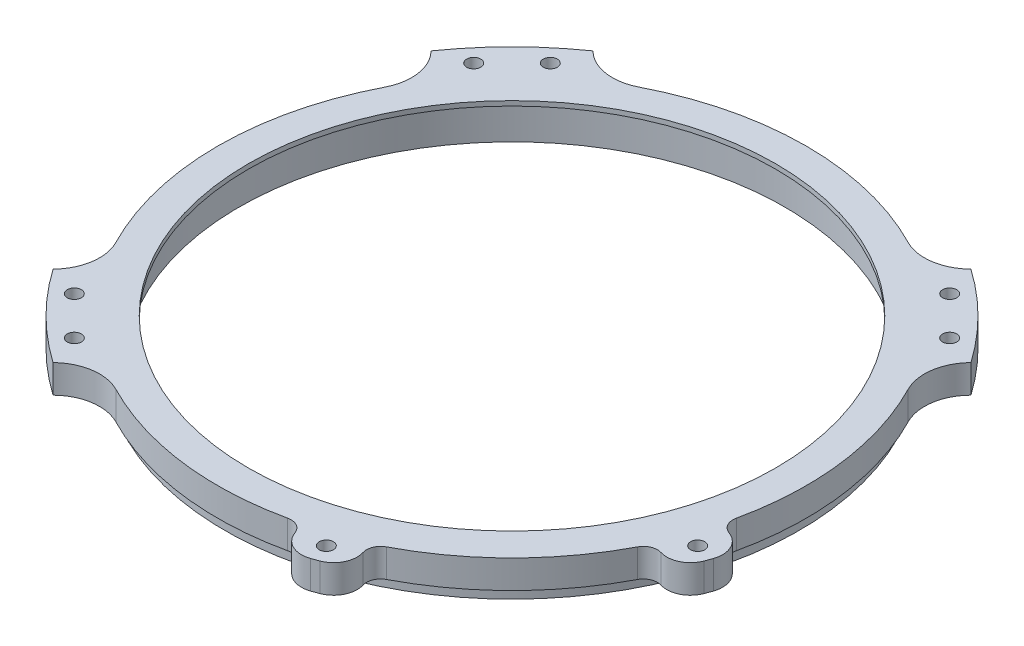
SolidWorks part; units mm, degrees
material "6061 合金"
ref_plane "前视基准面" through (0, 0, 0) normal (0, 0, 1) x (1, 0, 0)
ref_plane "上视基准面" through (0, 0, 0) normal (0, 1, 0) x (1, 0, 0)
ref_plane "右视基准面" through (0, 0, 0) normal (1, 0, 0) x (0, 0, -1)
sketch "草图1" plane through (0, 0, 0) normal (0, 1, 0) x (1, 0, 0)
  circle A0 centre (0, 0) radius 70
  circle A1 centre (0, 0) radius 58
  dimension "D1" = 140
  dimension "D2" = 116
extrude "凸台-拉伸1" add sketch "草图1" along normal blind 9
sketch "草图3" plane through (0, 0, 0) normal (0, -1, 0) x (1, 0, 0)
  circle A0 centre (0, 0) radius 70
  circle A1 centre (0, 0) radius 61
  dimension "D1" = 122
  dimension "D2" = 140
extrude "切除-拉伸2" cut sketch "草图3" against normal blind 3
sketch "草图4" plane through (0, 9, 0) normal (0, 1, 0) x (1, 0, 0)
  line L0 (0, 0) -> (0, 70) construction
  line L1 (35.8485, 51.197) -> (40.1504, 57.3406)
  line L2 (51.197, 35.8485) -> (57.3406, 40.1504)
  line L3 (60.3704, -16.1762) -> (67.6148, -18.1173)
  line L4 (16.1762, -60.3704) -> (18.1173, -67.6148)
  line L5 (-35.8485, -51.197) -> (-40.1504, -57.3406)
  line L6 (-51.197, -35.8485) -> (-57.3406, -40.1504)
  line L7 (-51.197, 35.8485) -> (-57.3406, 40.1504)
  line L8 (-35.8485, 51.197) -> (-40.1504, 57.3406)
  line L9 (0, 0) -> (35.8485, 51.197) construction
  line L10 (0, 0) -> (51.197, 35.8485) construction
  line L11 (16.1762, -60.3704) -> (0, 0) construction
  line L12 (60.3704, -16.1762) -> (0, 0) construction
  line L13 (0, 0) -> (0, -70) construction
  arc A0 (-51.197, 35.8485) -> (-51.197, -35.8485) centre (0, 0) ccw
  arc A1 (-57.3406, 40.1504) -> (-57.3406, -40.1504) centre (0, 0) ccw
  arc A2 (-35.8485, -51.197) -> (16.1762, -60.3704) centre (0, 0) ccw
  arc A3 (-40.1504, -57.3406) -> (18.1173, -67.6148) centre (0, 0) ccw
  arc A4 (60.3704, -16.1762) -> (51.197, 35.8485) centre (0, 0) ccw
  arc A5 (67.6148, -18.1173) -> (57.3406, 40.1504) centre (0, 0) ccw
  arc A6 (35.8485, 51.197) -> (-35.8485, 51.197) centre (0, 0) ccw
  arc A7 (40.1504, 57.3406) -> (-40.1504, 57.3406) centre (0, 0) ccw
  point P24 (0, 0)
  dimension "D1" = 125
  dimension "D5" = 70
  dimension "D2" = 35
  dimension "D3" = 20
  dimension "D6" = 15
  dimension "D4" = 60
extrude "切除-拉伸3" cut sketch "草图4" against normal through all
fillet "圆角1" radius 10 6 edges at (-51.197, 6, 35.8485) (-35.8485, 6, 51.197) (51.197, 6, -35.8485) (35.8485, 6, -51.197) (-35.8485, 6, -51.197) (-51.197, 6, -35.8485)
sketch "草图8" plane through (0, 9, 0) normal (0, 1, 0) x (1, 0, 0)
  line L0 (0, 0) -> (49.4975, -49.4975) construction
  line L1 (0, 0) -> (0, -70) construction
  line L2 (26.625, -57.0974) -> (29.5833, -63.4415)
  line L3 (26.625, -57.0974) -> (0, 0) construction
  line L4 (57.0974, -26.625) -> (63.4415, -29.5833)
  line L5 (57.0974, -26.625) -> (0, 0) construction
  arc A0 (26.625, -57.0974) -> (57.0974, -26.625) centre (0, 0) ccw
  arc A1 (29.5833, -63.4415) -> (63.4415, -29.5833) centre (0, 0) ccw
  dimension "D1" = 126
  dimension "D2" = 140
  dimension "D3" = 45
  dimension "D4" = 20
extrude "切除-拉伸6" cut sketch "草图8" against normal through all
fillet "圆角7" radius 3 4 edges at (60.3704, 6, 16.1762) (57.0974, 6, 26.625) (26.625, 6, 57.0974) (16.1762, 6, 60.3704)
sketch "草图6" plane through (0, 9, 0) normal (0, 1, 0) x (1, 0, 0)
  line L0 (0, 0) -> (0, 62.5) construction
  line L1 (0, 0) -> (42.424, 50.5589) construction
  line L2 (0, 0) -> (46.669, 46.669) construction
  line L3 (0, 0) -> (0, -66) construction
  line L4 (0, 0) -> (22.5733, -62.0197) construction
  line L5 (0, 0) -> (46.669, -46.669) construction
  arc A0 (28.5751, 55.5852) -> (-28.5751, 55.5852) centre (0, 0) ccw construction
  circle A1 centre (0, 0) radius 66 construction
  circle A2 centre (42.424, 50.5589) radius 1.5
  circle A4 centre (-42.424, -50.5589) radius 1.5
  circle A5 centre (-50.5589, 42.424) radius 1.5
  circle A6 centre (50.5589, 42.424) radius 1.5
  circle A8 centre (-50.5589, -42.424) radius 1.5
  circle A9 centre (-42.424, 50.5589) radius 1.5
  circle A10 centre (50.5589, -42.424) radius 1.5 [skipped]
  circle A11 centre (42.424, -50.5589) radius 1.5 [skipped]
  circle A12 centre (22.5733, -62.0197) radius 1.5
  circle A13 centre (62.0197, -22.5733) radius 1.5
  point P18 (0, 0)
  point P28 (0, 0)
  dimension "D1" = 132
  dimension "D3" = 3
  dimension "D7" = 3
  dimension "D2" = 40
  dimension "D5" = 45
  dimension "D8" = 20
  dimension "D4" = 4
  dimension "D6" = 4
extrude "切除-拉伸4" cut sketch "草图6" against normal blind 10
fillet "圆角9" radius 5 4 edges at (67.6148, 6, 18.1173) (63.4415, 6, 29.5833) (18.1173, 6, 67.6148) (29.5833, 6, 63.4415)
sketch "草图9" plane through (0, 9, 0) normal (0, 1, 0) x (1, 0, 0)
  circle A1 centre (0, 0) radius 56
  circle A2 centre (0, 0) radius 58
  dimension "D1" = 116
  dimension "D2" = 112
extrude "凸台-拉伸2" add sketch "草图9" against normal blind 1
